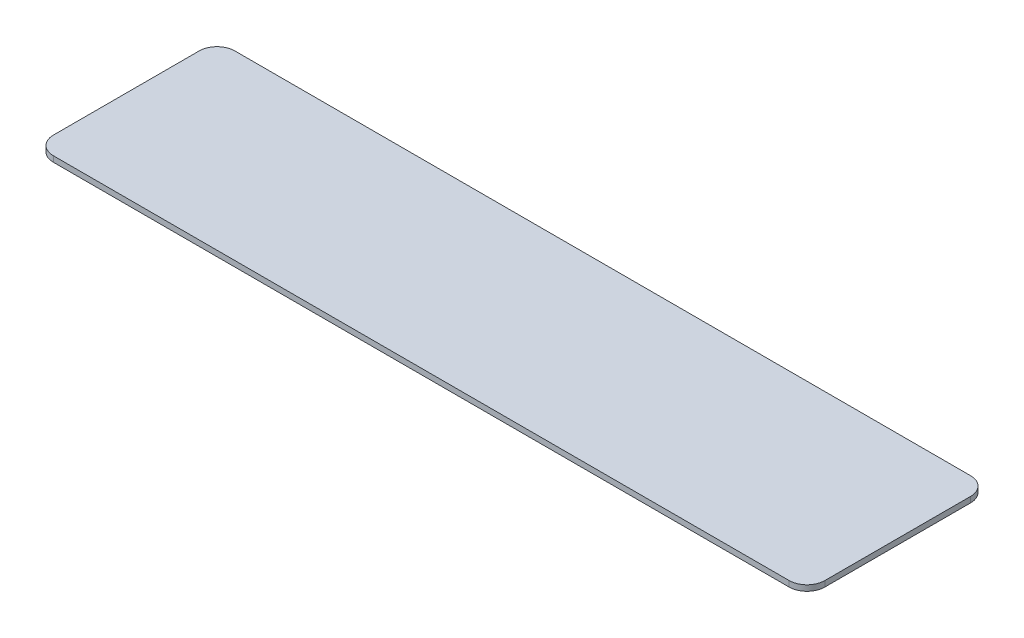
SolidWorks part; units mm, degrees
ref_plane "Front" through (0, 0, 0) normal (0, 0, 1) x (1, 0, 0)
ref_plane "Top" through (0, 0, 0) normal (0, 1, 0) x (1, 0, 0)
ref_plane "Right" through (0, 0, 0) normal (1, 0, 0) x (0, 0, -1)
sketch "Sketch1" plane through (0, 0, 0) normal (0, 1, 0) x (1, 0, 0)
  line L1 (-2.1325, 0) -> (429.6675, 0)
  line L2 (-2.1325, 0) -> (-2.1325, 101.6)
  line L3 (-2.1325, 101.6) -> (429.6675, 101.6)
  line L4 (429.6675, 0) -> (429.6675, 101.6)
  dimension "D1" = 101.6
  dimension "D2" = 431.8
extrude "Boss-Extrude1" add sketch "Sketch1" along normal blind 3.175
fillet "Fillet1" radius 10 4 edges at (429.6675, 1.5875, -101.6) (429.6675, 1.5875, 0) (-2.1325, 1.5875, 0) (-2.1325, 1.5875, -101.6)
